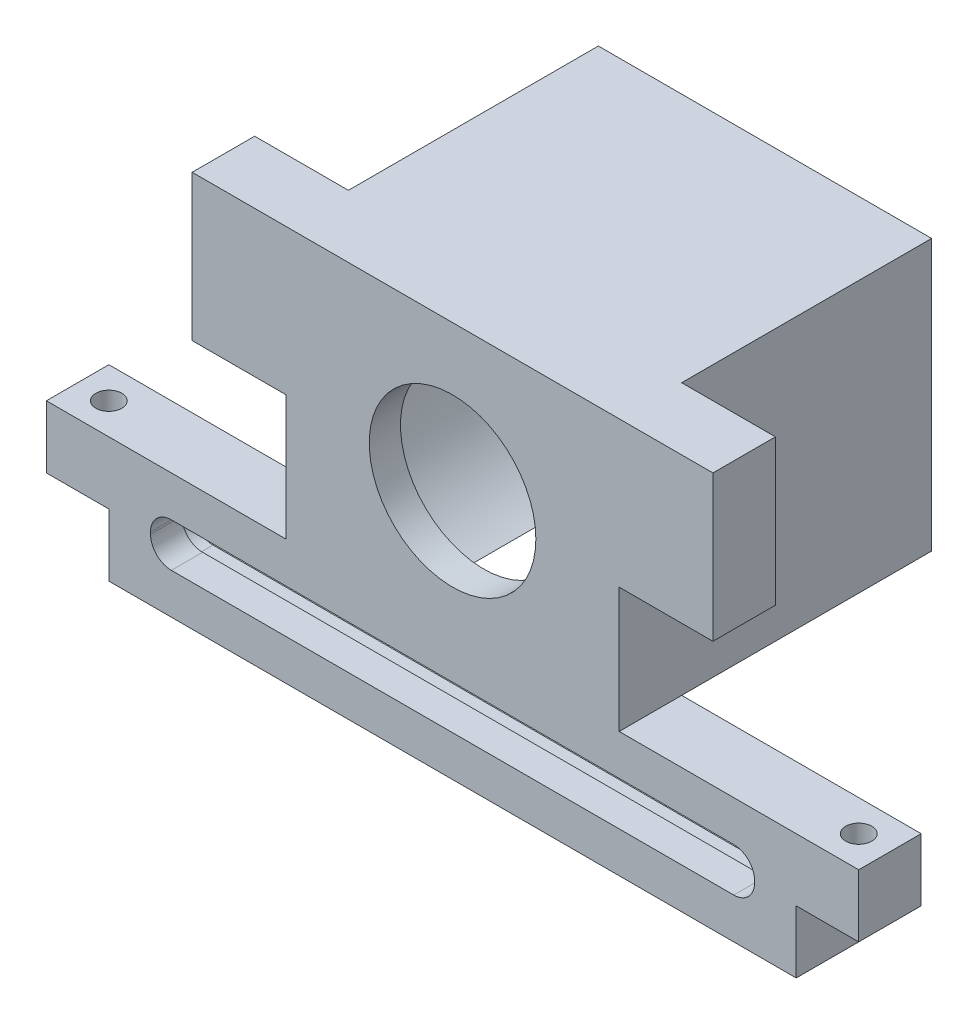
SolidWorks part; units mm, degrees
material "1060 Alloy"
ref_plane "Front Plane" through (0, 0, 0) normal (0, 0, 1) x (1, 0, 0)
ref_plane "Top Plane" through (0, 0, 0) normal (0, 1, 0) x (1, 0, 0)
ref_plane "Right Plane" through (0, 0, 0) normal (1, 0, 0) x (0, 0, -1)
sketch "Sketch1" plane through (0, 0, 0) normal (0, 0, 1) x (1, 0, 0)
  line L0 (23, 32) -> (55, 32)
  line L1 (6, 0) -> (6, -6)
  line L2 (55, 32) -> (55, 6)
  line L3 (23, 32) -> (23, 6)
  line L4 (10, 2.1) -> (68, 2.1)
  line L5 (10, 2.1) -> (10, -2.1)
  line L6 (10, -2.1) -> (68, -2.1)
  line L7 (68, 2.1) -> (68, -2.1)
  line L8 (6, -6) -> (72, -6)
  line L9 (72, -6) -> (72, 0)
  line L10 (6, 0) -> (0, 0)
  line L11 (0, 0) -> (0, 6)
  line L12 (0, 6) -> (23, 6)
  line L13 (55, 6) -> (78, 6)
  line L14 (78, 6) -> (78, 0)
  line L15 (78, 0) -> (72, 0)
  circle A0 centre (39, 18) radius 8
  dimension "D4" = 16
  dimension "D1" = 4.2
  dimension "D2" = 58
  dimension "D3" = 3.9
  dimension "D5" = 4
  dimension "D6" = 4
  dimension "D7" = 32
  dimension "D8" = 16
  dimension "D9" = 18
  dimension "D10" = 6
  dimension "D12" = 6
  dimension "D13" = 3.9
  dimension "D14" = 32
extrude "Boss-Extrude1" add sketch "Sketch1" along normal blind 30
sketch "Sketch3" plane through (0, 0, 0) normal (0, 0, -1) x (-1, 0, 0)
  circle A0 centre (-39, 18) radius 13
  dimension "D1" = 26
extrude "Cut-Extrude2" cut sketch "Sketch3" against normal offset from surface (27 mm away) 3 up to face at (39, 0, 30)
hole_wizard "Tap Drill for M3 Tap2" positions "Sketch5" profile "Sketch4" hole size "M3" standard "ISO"
sketch "Sketch5" plane through (38.1016, 0, -22.7468) normal (0, -1, 0) x (-1, 0, 0)
  line L3 (-39.8984, -52.7468) -> (-39.8984, -22.7468) construction
  line L4 (38.1016, -52.7468) -> (38.1016, -22.7468) construction
  line L5 (-33.8984, -52.7468) -> (-39.8984, -52.7468) construction
  point P0 (35.1016, -49.7468)
  point P2 (-36.8984, -49.7468)
  dimension "D1" = 3
  dimension "D2" = 3
  dimension "D3" = 3
sketch "Sketch4" plane through (3, 0, 27) normal (1, 0, 0) x (0, 0, -1)
  line L0 (0, 0) -> (0, 8.7511)
  line L1 (0, 8.7511) -> (1.25, 8)
  line L2 (1.25, 8) -> (1.25, 0)
  line L5 (1.25, 0) -> (0, 0)
  line L10 (0, 8.7511) -> (-1.25, 8) construction
  line L11 (0, -6.35) -> (0, 107.95) construction
  dimension "Hole Dia." = 2.5
  dimension "Hole Depth" = 8
  dimension "Drill Angle" = 118
sketch "Sketch6" plane through (0, 0, 0) normal (0, 0, -1) x (-1, 0, 0)
  line L2 (-78, 6) -> (0, 6)
  line L3 (-78, 6) -> (-78, -6)
  line L4 (-78, -6) -> (0, -6)
  line L5 (0, 6) -> (0, -6)
extrude "Cut-Extrude3" cut sketch "Sketch6" along direction (0, 0, 1) on the side against the normal offset from surface (24 mm away) 6 up to face at (39, 0, 30)
sketch "Sketch10" plane through (0, 0, 24) normal (0, 0, -1) x (-1, 0, 0)
  line L1 (-70, 4) -> (-8, 4)
  line L2 (-70, 4) -> (-70, -4)
  line L3 (-70, -4) -> (-8, -4)
  line L4 (-8, 4) -> (-8, -4)
  line L5 (-68, 2.1) -> (-10, 2.1) construction
  line L6 (-68, -2.1) -> (-68, 2.1) construction
  line L7 (-10, 2.1) -> (-10, -2.1) construction
  dimension "D1" = 8
  dimension "D2" = 1.9
  dimension "D3" = 2
  dimension "D4" = 2
extrude "Cut-Extrude5" cut sketch "Sketch10" against normal blind 3
sketch "Sketch11" plane through (0, 0, 30) normal (0, 0, 1) x (1, 0, 0)
  line L0 (23, 6) -> (0, 6) construction
  line L1 (23, 32) -> (14, 32)
  line L2 (23, 32) -> (23, 6)
  line L3 (23, 6) -> (14, 6)
  line L4 (14, 32) -> (14, 6)
  line L5 (78, 6) -> (55, 6) construction
  line L6 (55, 32) -> (64, 32)
  line L7 (55, 32) -> (55, 6)
  line L8 (55, 6) -> (64, 6)
  line L9 (64, 32) -> (64, 6)
  dimension "D1" = 50
extrude "Boss-Extrude2" add sketch "Sketch11" against normal up to surface (6 mm away) up to face at (39, 0, 24)
sketch "Sketch12" plane through (0, 0, 24) normal (0, 0, -1) x (-1, 0, 0)
  line L0 (-55, 6) -> (-55, 32) construction
  line L1 (-64, 6) -> (-55, 6)
  line L2 (-64, 6) -> (-64, 18)
  line L3 (-64, 18) -> (-55, 18)
  line L4 (-55, 6) -> (-55, 18)
  line L5 (-23, 32) -> (-23, 6) construction
  line L6 (-14, 6) -> (-23, 6)
  line L7 (-14, 6) -> (-14, 18)
  line L8 (-14, 18) -> (-23, 18)
  line L9 (-23, 6) -> (-23, 18)
  dimension "D1" = 12
extrude "Cut-Extrude6" cut sketch "Sketch12" against normal up to next
fillet "Fillet1" radius 2 8 edges at (8, -4, 25.5) (10, -2.1, 28.5) (8, 4, 25.5) (10, 2.1, 28.5) (70, -4, 25.5) (70, 4, 25.5) (68, -2.1, 28.5) (68, 2.1, 28.5)
